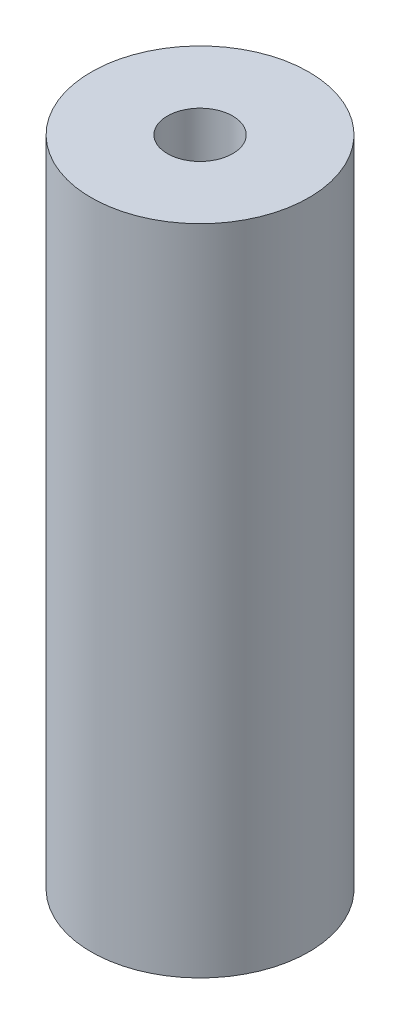
SolidWorks part; units mm, degrees
ref_plane "Front Plane" through (0, 0, 0) normal (0, 0, 1) x (1, 0, 0)
ref_plane "Top Plane" through (0, 0, 0) normal (0, 1, 0) x (1, 0, 0)
ref_plane "Right Plane" through (0, 0, 0) normal (1, 0, 0) x (0, 0, -1)
sketch "Sketch1" plane through (0, 0, 0) normal (0, 0, 1) x (1, 0, 0)
  line L0 (0, 0) -> (0, 5.7533) construction
  line L1 (-0.75, 15) -> (-0.75, 8)
  line L2 (-0.75, 8) -> (-1.5, 8)
  line L3 (-1.5, 8) -> (-1.5, 0)
  line L4 (-1.5, 0) -> (-2.5, 0)
  line L5 (-2.5, 0) -> (-2.5, 15)
  line L6 (-2.5, 15) -> (-0.75, 15)
  dimension "D1" = 3
  dimension "D2" = 5
  dimension "D3" = 1.5
  dimension "D4" = 7
  dimension "D5" = 8
  dimension "D6" = 15
revolve "Revolve1" add sketch "Sketch1" angle 360 about L0
